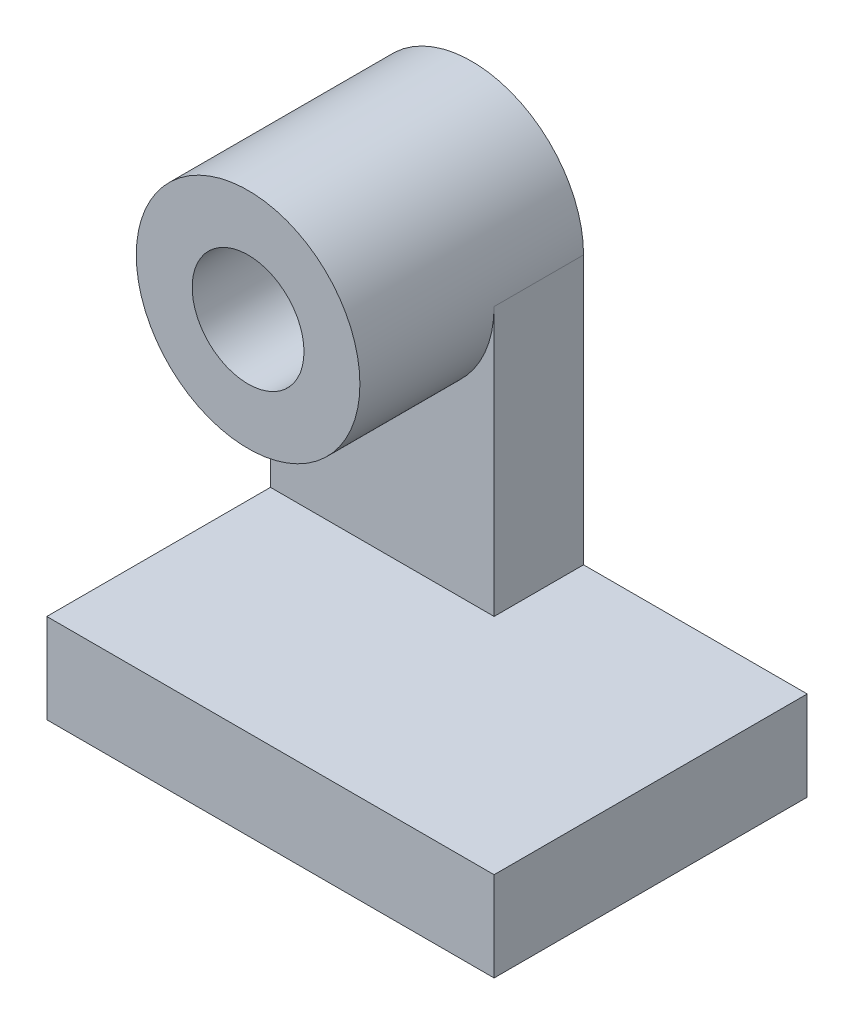
SolidWorks part; units mm, degrees
material "Plain Carbon Steel"
ref_plane "Front Plane" through (0, 0, 0) normal (0, 0, 1) x (1, 0, 0)
ref_plane "Top Plane" through (0, 0, 0) normal (0, 1, 0) x (1, 0, 0)
ref_plane "Right Plane" through (0, 0, 0) normal (1, 0, 0) x (0, 0, -1)
sketch "Sketch1" plane through (0, 0, 0) normal (0, 0, 1) x (1, 0, 0)
  line L1 (0, 0) -> (127, 0)
  line L2 (0, 0) -> (0, 25.4)
  line L3 (0, 25.4) -> (127, 25.4)
  line L4 (127, 0) -> (127, 25.4)
  line L5 (0, 25.4) -> (63.5, 25.4)
  line L6 (0, 25.4) -> (0, 101.6)
  line L7 (0, 101.6) -> (63.5, 101.6)
  line L8 (63.5, 25.4) -> (63.5, 101.6)
  circle A0 centre (31.75, 101.6) radius 31.75
  circle A1 centre (31.75, 101.6) radius 15.875
  dimension "D4" = 63.5
  dimension "D5" = 31.75
  dimension "D1" = 127
  dimension "D2" = 25.4
  dimension "D3" = 101.6
extrude "Boss-Extrude1" add sketch "Sketch1" along normal blind 88.9 contours L3 L4 L1 L2
extrude "Boss-Extrude2" add sketch "Sketch1<3>" along normal blind 25.4 contours A0 L6 L3 L8 region at (31.75, 51.5216, 0)
sketch "Sketch1<3>" plane through (0, 0, 0) normal (0, 0, 1) x (1, 0, 0) same geometry as "Sketch1"
extrude "Boss-Extrude3" add sketch "Sketch1<4>" along normal blind 63.5 contours A1 L7 A0 | A1 L7 A0 region at (31.75, 132.64, 0) region at (7.9375, 100.89, 0)
sketch "Sketch1<4>" plane through (0, 0, 0) normal (0, 0, 1) x (1, 0, 0) same geometry as "Sketch1"
